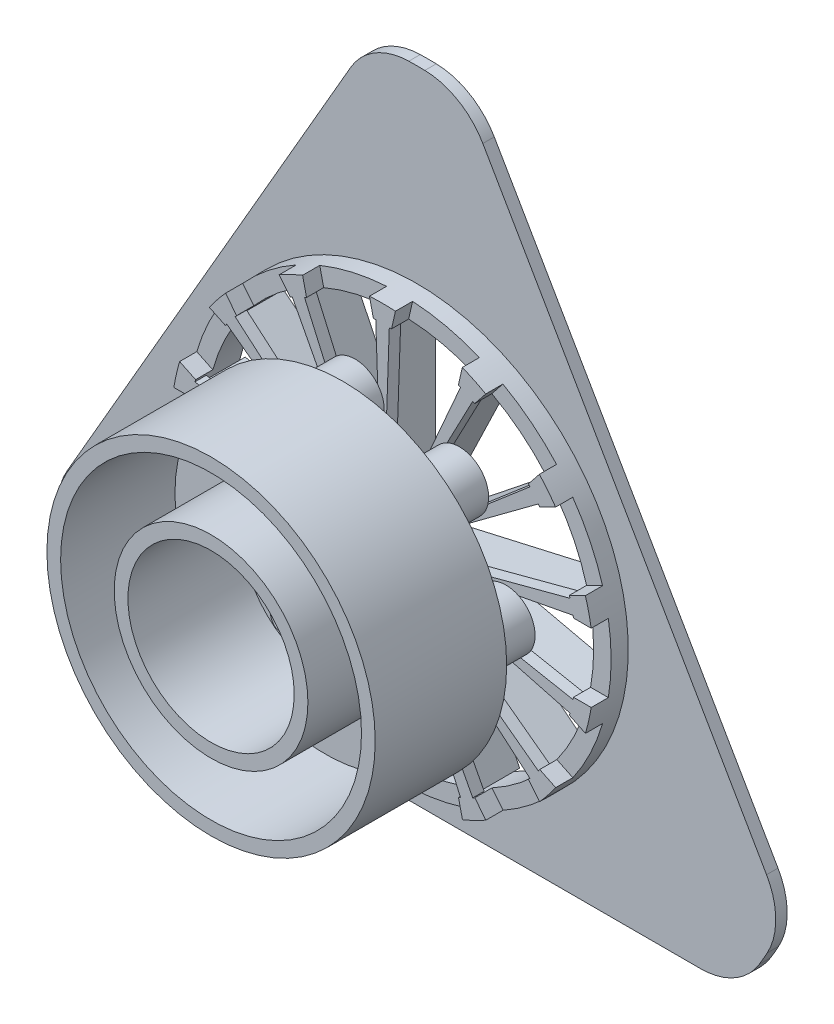
SolidWorks part; units mm, degrees
ref_plane "Спереди" through (0, 0, 0) normal (0, 0, 1) x (1, 0, 0)
ref_plane "Сверху" through (0, 0, 0) normal (0, 1, 0) x (1, 0, 0)
ref_plane "Справа" through (0, 0, 0) normal (1, 0, 0) x (0, 0, -1)
sketch "Sketch1" plane through (0, 0, 0) normal (0, 0, 1) x (1, 0, 0)
  line L0 (3.9, 6.755) -> (7.8, 0) construction
  line L2 (5.85, 10.1325) -> (11.7, 0) construction
  line L4 (7.8, 13.51) -> (15.6, 0) construction
  circle A61 centre (0, 0) radius 20
  circle A131 centre (0, 0) radius 1.25
  circle A484 centre (3.9, 0) radius 1.25
  circle A485 centre (7.8, 0) radius 1.25
  circle A486 centre (11.7, 0) radius 1.25
  circle A487 centre (15.6, 0) radius 1.25
  circle A488 centre (1.95, -3.3775) radius 1.25
  circle A489 centre (3.9, -6.755) radius 1.25
  circle A490 centre (5.85, -10.1325) radius 1.25
  circle A491 centre (7.8, -13.51) radius 1.25
  circle A492 centre (-1.95, -3.3775) radius 1.25
  circle A493 centre (-3.9, -6.755) radius 1.25
  circle A494 centre (-5.85, -10.1325) radius 1.25
  circle A495 centre (-7.8, -13.51) radius 1.25
  circle A496 centre (-3.9, 0) radius 1.25
  circle A497 centre (-7.8, 0) radius 1.25
  circle A498 centre (-11.7, 0) radius 1.25
  circle A499 centre (-15.6, 0) radius 1.25
  circle A500 centre (-1.95, 3.3775) radius 1.25
  circle A501 centre (-3.9, 6.755) radius 1.25
  circle A502 centre (-5.85, 10.1325) radius 1.25
  circle A503 centre (-7.8, 13.51) radius 1.25
  circle A504 centre (1.95, 3.3775) radius 1.25
  circle A505 centre (3.9, 6.755) radius 1.25
  circle A506 centre (5.85, 10.1325) radius 1.25
  circle A507 centre (7.8, 13.51) radius 1.25
  circle A508 centre (5.85, 3.3775) radius 1.25
  circle A509 centre (7.8, 6.755) radius 1.25
  circle A510 centre (9.75, 3.3775) radius 1.25
  circle A511 centre (11.7, 6.755) radius 1.25
  circle A512 centre (9.7491, 10.1341) radius 1.25
  circle A513 centre (13.6509, 3.3759) radius 1.25
  circle A514 centre (5.85, -3.3791) radius 1.25
  circle A515 centre (9.75, -3.3791) radius 1.25
  circle A516 centre (7.8, -6.7566) radius 1.25
  circle A517 centre (11.7, -6.7566) radius 1.25
  circle A518 centre (9.7491, -10.1356) radius 1.25
  circle A519 centre (13.6509, -3.3775) radius 1.25
  circle A520 centre (-0.0013, -6.7573) radius 1.25
  circle A521 centre (1.9487, -10.1348) radius 1.25
  circle A522 centre (-1.9513, -10.1348) radius 1.25
  circle A523 centre (-0.0013, -13.5123) radius 1.25
  circle A524 centre (-3.9032, -13.5123) radius 1.25
  circle A525 centre (3.9005, -13.5123) radius 1.25
  circle A526 centre (-5.8527, -3.3791) radius 1.25
  circle A527 centre (-7.8027, -6.7566) radius 1.25
  circle A528 centre (-9.7527, -3.3791) radius 1.25
  circle A529 centre (-11.7027, -6.7566) radius 1.25
  circle A530 centre (-13.6536, -3.3775) radius 1.25
  circle A531 centre (-9.7518, -10.1356) radius 1.25
  circle A532 centre (-5.8527, 3.3775) radius 1.25
  circle A533 centre (-9.7527, 3.3775) radius 1.25
  circle A534 centre (-7.8027, 6.755) radius 1.25
  circle A535 centre (-11.7027, 6.755) radius 1.25
  circle A536 centre (-9.7518, 10.1341) radius 1.25
  circle A537 centre (-13.6536, 3.3759) radius 1.25
  circle A538 centre (-0.0014, 6.7558) radius 1.25
  circle A539 centre (-1.9514, 10.1333) radius 1.25
  circle A540 centre (1.9486, 10.1333) radius 1.25
  circle A541 centre (-0.0014, 13.5108) radius 1.25
  circle A542 centre (3.9005, 13.5108) radius 1.25
  circle A543 centre (-3.9032, 13.5108) radius 1.25
  circle A544 centre (13.65, -1.1258) radius 2.2517 construction
  circle A545 centre (11.7009, -4.5044) radius 2.2522 construction
  circle A546 centre (9.75, -7.8834) radius 2.2522 construction
  circle A547 centre (7.7987, -11.2591) radius 2.2509 construction
  circle A548 centre (13.65, -1.1258) radius 0.65
  circle A549 centre (11.7009, -4.5044) radius 0.65
  circle A550 centre (9.75, -7.8834) radius 0.65
  circle A551 centre (7.7987, -11.2591) radius 0.65
  circle A552 centre (9.75, -1.1258) radius 0.65
  circle A553 centre (7.8009, -4.5044) radius 0.65
  circle A554 centre (5.85, -7.8834) radius 0.65
  circle A555 centre (3.8987, -11.2591) radius 0.65
  circle A556 centre (5.85, -1.1258) radius 0.65
  circle A557 centre (3.9009, -4.5044) radius 0.65
  circle A558 centre (1.95, -7.8834) radius 0.65
  circle A559 centre (-0.0013, -11.2591) radius 0.65
  circle A560 centre (1.95, -1.1258) radius 0.65
  circle A561 centre (0.0009, -4.5044) radius 0.65
  circle A562 centre (-1.95, -7.8834) radius 0.65
  circle A563 centre (-3.9013, -11.2591) radius 0.65
  circle A564 centre (-1.95, -1.1258) radius 0.65
  circle A565 centre (-3.8991, -4.5044) radius 0.65
  circle A566 centre (-5.85, -7.8834) radius 0.65
  circle A567 centre (-7.8013, -11.2591) radius 0.65
  circle A568 centre (-5.85, -1.1258) radius 0.65
  circle A569 centre (-7.7991, -4.5044) radius 0.65
  circle A570 centre (-9.75, -7.8834) radius 0.65
  circle A572 centre (-9.75, -1.1258) radius 0.65
  circle A573 centre (-11.6991, -4.5044) radius 0.65
  circle A576 centre (-13.65, -1.1258) radius 0.65
  circle A587 centre (0, 2.2517) radius 2.2517 construction
  circle A588 centre (0, 2.2517) radius 0.65
  circle A589 centre (3.9, 2.2517) radius 0.65
  circle A590 centre (7.8, 2.2517) radius 0.65
  circle A591 centre (11.7, 2.2517) radius 0.65
  circle A592 centre (15.6, 2.2517) radius 0.65
  circle A593 centre (1.9491, 5.6297) radius 2.2522 construction
  circle A594 centre (1.9491, 5.6297) radius 0.65
  circle A595 centre (5.8491, 5.6297) radius 0.65
  circle A596 centre (9.7491, 5.6297) radius 0.65
  circle A597 centre (13.6491, 5.6297) radius 0.65
  circle A598 centre (3.8991, 9.0072) radius 2.2522 construction
  circle A599 centre (3.8991, 9.0072) radius 0.65
  circle A600 centre (7.7991, 9.0072) radius 0.65
  circle A601 centre (11.6991, 9.0072) radius 0.65
  circle A602 centre (5.85, 12.3842) radius 2.2517 construction
  circle A603 centre (5.85, 12.3842) radius 0.65
  circle A604 centre (9.75, 12.3842) radius 0.65
  circle A605 centre (5.85, -14.6358) radius 0.65
  circle A606 centre (1.9509, -14.6353) radius 0.65
  circle A607 centre (-1.9491, -14.6353) radius 0.65
  circle A608 centre (-5.85, -14.6358) radius 0.65
  circle A609 centre (-15.6, 2.2517) radius 0.65
  circle A610 centre (-13.65, 5.6281) radius 0.65
  circle A611 centre (-11.7, 9.0056) radius 0.65
  circle A612 centre (-9.75, 12.3842) radius 0.65
  circle A613 centre (-5.85, 12.3842) radius 0.65
  circle A614 centre (-1.95, 12.3842) radius 0.65
  circle A615 centre (1.95, 12.3842) radius 0.65
  circle A616 centre (-7.8, 9.0056) radius 0.65
  circle A617 centre (-9.75, 5.6281) radius 0.65
  circle A618 centre (-11.7, 2.2517) radius 0.65
  circle A619 centre (-3.9, 9.0056) radius 0.65
  circle A620 centre (-5.85, 5.6281) radius 0.65
  circle A621 centre (-7.8, 2.2517) radius 0.65
  circle A622 centre (0, 9.0056) radius 0.65
  circle A623 centre (-1.95, 5.6281) radius 0.65
  circle A624 centre (-3.9, 2.2517) radius 0.65
  circle A625 centre (-15.5991, -4.5044) radius 0.65
  circle A626 centre (-13.65, -7.8834) radius 0.65
  circle A627 centre (-17.55, -7.8834) radius 0.65
  circle A628 centre (-19.5013, -11.2591) radius 0.65
  circle A629 centre (-15.6013, -11.2591) radius 0.65
  circle A630 centre (-11.7013, -11.2591) radius 0.65
  point P51 (0, 0)
  point P125 (-0.0013, -0.0008)
  point P231 (0, 0)
  dimension "D1" = 5
  dimension "D3" = 6
  dimension "D5" = 8
  dimension "D7" = 4
  dimension "D11" = 4
  dimension "D2" = 6
  dimension "D6" = 5
  dimension "D8" = 3
  dimension "D9" = 2
  dimension "D4" = 1.3
  dimension "D10" = 3
ref_plane "Plane1" through (0, 0, 10) normal (0, 0, 1) x (1, 0, 0)
sketch "Sketch2" plane through (0, 0, 10) normal (0, 0, 1) x (1, 0, 0)
  line L0 (0, 15.7191) -> (0, 7.2245) construction
  line L62 (-0.15, 16.9697) -> (-0.15, 0.6837)
  line L71 (0.15, 16.9697) -> (0.15, 0.6837)
  line L92 (7.498, 15.2241) -> (0.4318, 0.5509)
  line L101 (7.2278, 15.3543) -> (0.1615, 0.6811)
  line L110 (13.361, 10.4632) -> (0.6281, 0.309)
  line L119 (13.174, 10.6977) -> (0.441, 0.5436)
  line L124 (16.5777, 3.6299) -> (0.7, 0.0059)
  line L133 (16.5109, 3.9224) -> (0.6332, 0.2984)
  line L142 (16.5109, -3.9224) -> (0.6332, -0.2984)
  line L151 (16.5777, -3.6299) -> (0.7, -0.0059)
  line L160 (13.174, -10.6977) -> (0.441, -0.5436)
  line L165 (13.361, -10.4632) -> (0.6281, -0.309)
  line L168 (7.2278, -15.3543) -> (0.1615, -0.6811)
  line L171 (7.498, -15.2241) -> (0.4318, -0.5509)
  line L174 (-0.15, -16.9697) -> (-0.15, -0.6837)
  line L177 (0.15, -16.9697) -> (0.15, -0.6837)
  line L180 (-7.498, -15.2241) -> (-0.4318, -0.5509)
  line L183 (-7.2278, -15.3543) -> (-0.1615, -0.6811)
  line L186 (-13.361, -10.4632) -> (-0.6281, -0.309)
  line L189 (-13.174, -10.6977) -> (-0.441, -0.5436)
  line L192 (-16.5777, -3.6299) -> (-0.7, -0.0059)
  line L193 (-16.5109, -3.9224) -> (-0.6332, -0.2984)
  line L194 (-16.5109, 3.9224) -> (-0.6332, 0.2984)
  line L195 (-16.5777, 3.6299) -> (-0.7, 0.0059)
  line L196 (-13.174, 10.6977) -> (-0.441, 0.5436)
  line L197 (-13.361, 10.4632) -> (-0.6281, 0.309)
  line L198 (-7.2278, 15.3543) -> (-0.1615, 0.6811)
  line L199 (-7.498, 15.2241) -> (-0.4318, 0.5509)
  circle A52 centre (0, 0) radius 16.9704
  circle A53 centre (0, 0) radius 18.5
  circle A199 centre (0, 0) radius 0.7
  point P62 (0, 0)
  dimension "D1" = 0.3
extrude "Boss-Extrude10" add sketch "Sketch2" along normal blind 4 contours A53 A52 | A199 L71 A52 L62 | A199 L92 A52 L101 | A199 L110 A52 L119 | A199 L124 A52 L133 | A199 L142 A52 L151 | A199 L160 A52 L165 | A199 L168 A52 L171 | A199 L174 A52 L177 | A199 L180 A52 L183 | A199 L186 A52 L189 | A199 L192 A52 L193 | A199 L196 A52 L197 | A199 L198 A52 L199 | A199 L194 A52 L195 | A199 region at (0, 8.8324, 10) region at (0, 0, 10) region at (-3.8322, 7.9577, 10) region at (3.8322, 7.9577, 10) region at (-6.9054, 5.5069, 10) region at (6.9054, 5.5069, 10) region at (-8.6109, 1.9654, 10) region at (8.6109, 1.9654, 10) region at (-8.6109, -1.9654, 10) region at (8.6109, -1.9654, 10) region at (-6.9054, -5.5069, 10) region at (6.9054, -5.5069, 10) region at (-3.8322, -7.9577, 10) region at (3.8322, -7.9577, 10) region at (0, -8.8324, 10) region at (-17.9767, 0, 10)
sketch "Sketch8" plane through (0, 0, 14) normal (0, 0, 1) x (1, 0, 0)
  circle A0 centre (0, 0) radius 21.2494
  circle A1 centre (0, 0) radius 22.6785
extrude "Boss-Extrude11" add sketch "Sketch8" against normal blind 4 separate body
sketch "Sketch9" plane through (0, 0, 14) normal (0, 0, 1) x (1, 0, 0)
  line L0 (-7.2278, 15.3543) -> (-0.1615, 0.6811) construction
  line L2 (13.361, 10.4632) -> (0.6281, 0.309) construction
  line L3 (7.2278, 15.3543) -> (0.1615, 0.6811) construction
  line L7 (-13.361, 10.4632) -> (-0.6281, 0.309) construction
  circle A0 centre (1.4743, 6.4592) radius 1.6243
  circle A1 centre (1.4743, 6.4592) radius 1.1243
  circle A2 centre (5.9692, 2.8746) radius 1.6243
  circle A3 centre (5.9692, 2.8746) radius 1.1243
  circle A4 centre (5.9692, -2.8746) radius 1.6243
  circle A5 centre (5.9692, -2.8746) radius 1.1243
  circle A6 centre (1.4743, -6.4592) radius 1.6243
  circle A7 centre (1.4743, -6.4592) radius 1.1243
  circle A8 centre (-4.1308, -5.1798) radius 1.6243
  circle A9 centre (-4.1308, -5.1798) radius 1.1243
  circle A10 centre (-6.6253, 0) radius 1.6243
  circle A11 centre (-6.6253, 0) radius 1.1243
  circle A12 centre (-4.1308, 5.1798) radius 1.6243
  circle A13 centre (-4.1308, 5.1798) radius 1.1243
  circle A14 centre (6.731, 8.4404) radius 2.5523
  circle A15 centre (6.731, 8.4404) radius 2.5523
  circle A16 centre (6.731, 8.4404) radius 2.0523
  circle A17 centre (10.7957, 0) radius 2.0523
  circle A18 centre (10.7957, 0) radius 2.5523
  circle A19 centre (6.731, -8.4404) radius 2.0523
  circle A20 centre (6.731, -8.4404) radius 2.5523
  circle A21 centre (-2.4023, -10.5251) radius 2.0523
  circle A22 centre (-2.4023, -10.5251) radius 2.5523
  circle A23 centre (-9.7266, -4.6841) radius 2.0523
  circle A24 centre (-9.7266, -4.6841) radius 2.5523
  circle A25 centre (-9.7266, 4.6841) radius 2.0523
  circle A26 centre (-9.7266, 4.6841) radius 2.5523
  circle A27 centre (-2.4023, 10.5251) radius 2.0523
  circle A28 centre (-2.4023, 10.5251) radius 2.5523
  point P24 (0, 0)
  point P30 (0, 0)
  point P31 (6.4938, 8.1493)
  point P51 (0, 0)
  point P57 (6.8199, 8.5519)
  point P58 (0, -0.3643)
  point P59 (0, 0)
  point P60 (0, 0)
  point P62 (1.4361, 6.3255)
  point P63 (1.629, 6.6904)
  point P64 (1.5046, 6.5918)
  point P65 (1.4701, 5.9808)
  dimension "D3" = 0.5
  dimension "D4" = 0.5
  dimension "D1" = 7
  dimension "D2" = 7
extrude "Boss-Extrude12" add sketch "Sketch9" along normal blind 5 contours A0 A1 | A14 A16 | A28 A27 | A12 A13 | A26 A25 | A10 A11 | A24 A23 | A8 A9 | A22 A21 | A20 A19 | A4 A5 | A6 A7 | A2 A3 | A18 A17 region at (-0.1041, 6.4592, 14) region at (4.3908, 2.8746, 14) region at (4.3908, -2.8746, 14) region at (-0.1041, -6.4592, 14) region at (-5.7091, -5.1798, 14) region at (-8.2036, 0, 14) region at (-5.7091, 5.1798, 14) region at (4.2509, 8.4404, 14) region at (8.3156, 0, 14) region at (4.2509, -8.4404, 14) region at (-4.8824, -10.5251, 14) region at (-12.2067, -4.6841, 14) region at (-12.2067, 4.6841, 14) region at (-4.8824, 10.5251, 14)
sketch "Sketch11" plane through (0, 0, 19) normal (0, 0, 1) x (1, 0, 0)
  circle A0 centre (0, 0) radius 8.1149
  circle A2 centre (0, 0) radius 4.8946
  circle A3 centre (0, 0) radius 14.3613
  circle M6 centre (10.7957, 0) radius 2.0523
  circle M7 centre (10.7957, 0) radius 2.5523
extrude "Boss-Extrude16" add sketch "Sketch11" against normal blind 1.5 contours A2 | A0 A2 | A3 A0 M7 | M6 region at (-7.8854, 0, 19) region at (0, 0, 19) region at (-13.9551, 0, 19) region at (10.7957, 0, 19)
sketch "Sketch12" plane through (0, 0, 19) normal (0, 0, 1) x (1, 0, 0)
  circle A0 centre (0, 0) radius 7.2737
  circle A1 centre (0, 0) radius 8.4737
  circle A2 centre (0, 0) radius 14.3613
  circle A3 centre (0, 0) radius 13.1613
  circle A6 centre (0, 0) radius 14.3613 construction
  dimension "D1" = 1.2
  dimension "D2" = 1.2
extrude "Boss-Extrude14" add sketch "Sketch12" along normal blind 10 contours A1 A0 | A2 A3 region at (-8.234, 0, 19) region at (-13.9551, 0, 19)
sketch "Sketch13" plane through (0, 0, 19) normal (0, 0, 1) x (1, 0, 0)
  circle A0 centre (1.355, 6.1475) radius 0.9
  circle A1 centre (5.6511, 2.7735) radius 0.9
  circle A2 centre (5.6919, -2.689) radius 0.9
  circle A3 centre (1.4465, -6.1266) radius 0.9
  circle A4 centre (-3.8881, -4.9508) radius 0.9
  circle A5 centre (-6.2949, -0.0469) radius 0.9
  circle A6 centre (-3.9615, 4.8923) radius 0.9
  circle A7 centre (-2.4023, 10.5251) radius 0.9
  circle A8 centre (6.8199, 8.5519) radius 0.9
  circle A9 centre (11.0272, 0.1115) radius 0.9
  circle A10 centre (7.0513, -8.4404) radius 0.9
  circle A11 centre (-2.1137, -10.664) radius 0.9
  circle A12 centre (-9.5664, -4.8849) radius 0.9
  circle A13 centre (-9.6949, 4.5451) radius 0.9
  point P4 (1.355, 6.1475)
  point P17 (0, 0)
  point P32 (0.1602, -0.0366)
extrude "Cut-Extrude2" cut sketch "Sketch13" against normal blind 1.5
sketch "Sketch16" plane through (0, 0, 10) normal (0, 0, -1) x (-1, 0, 0)
  line L0 (0, 0) -> (-0.5923, 16.9601)
  line L1 (0, 0) -> (0.5923, 16.9601)
  line L2 (0, 0) -> (7.8923, 15.0235)
  line L3 (0, 0) -> (6.8251, 15.5375)
  line L4 (0, 0) -> (13.6292, 10.1114)
  line L5 (0, 0) -> (12.8907, 11.0375)
  line L6 (0, 0) -> (16.6666, 3.1966)
  line L7 (0, 0) -> (16.4031, 4.3514)
  line L8 (0, 0) -> (16.4031, -4.3514)
  line L9 (0, 0) -> (16.6666, -3.1966)
  line L10 (0, 0) -> (12.8907, -11.0375)
  line L11 (0, 0) -> (13.6292, -10.1114)
  line L12 (0, 0) -> (6.8251, -15.5375)
  line L13 (0, 0) -> (7.8923, -15.0235)
  line L14 (0, 0) -> (-0.5923, -16.9601)
  line L15 (0, 0) -> (0.5923, -16.9601)
  line L16 (0, 0) -> (-7.8923, -15.0235)
  line L17 (0, 0) -> (-6.8251, -15.5375)
  line L18 (0, 0) -> (-13.6292, -10.1114)
  line L19 (0, 0) -> (-12.8907, -11.0375)
  line L20 (0, 0) -> (-16.6666, -3.1966)
  line L21 (0, 0) -> (-16.4031, -4.3514)
  line L22 (0, 0) -> (-16.4031, 4.3514)
  line L23 (0, 0) -> (-16.6666, 3.1966)
  line L24 (0, 0) -> (-12.8907, 11.0375)
  line L25 (0, 0) -> (-13.6292, 10.1114)
  line L26 (0, 0) -> (-6.8251, 15.5375)
  line L27 (0, 0) -> (-7.8923, 15.0235)
  arc A0 (-0.15, 16.9697) -> (-7.2278, 15.3543) centre (0, 0) ccw construction
  arc A1 (7.2278, 15.3543) -> (0.15, 16.9697) centre (0, 0) ccw construction
  arc A2 (-0.5923, 16.9601) -> (0.5923, 16.9601) centre (0, 0) cw
  arc A3 (6.8251, 15.5375) -> (7.8923, 15.0235) centre (0, 0) cw
  arc A4 (12.8907, 11.0375) -> (13.6292, 10.1114) centre (0, 0) cw
  arc A5 (16.4031, 4.3514) -> (16.6666, 3.1966) centre (0, 0) cw
  arc A6 (16.6666, -3.1966) -> (16.4031, -4.3514) centre (0, 0) cw
  arc A7 (13.6292, -10.1114) -> (12.8907, -11.0375) centre (0, 0) cw
  arc A8 (7.8923, -15.0235) -> (6.8251, -15.5375) centre (0, 0) cw
  arc A9 (0.5923, -16.9601) -> (-0.5923, -16.9601) centre (0, 0) cw
  arc A10 (-6.8251, -15.5375) -> (-7.8923, -15.0235) centre (0, 0) cw
  arc A11 (-12.8907, -11.0375) -> (-13.6292, -10.1114) centre (0, 0) cw
  arc A12 (-16.4031, -4.3514) -> (-16.6666, -3.1966) centre (0, 0) cw
  arc A13 (-16.6666, 3.1966) -> (-16.4031, 4.3514) centre (0, 0) cw
  arc A14 (-13.6292, 10.1114) -> (-12.8907, 11.0375) centre (0, 0) cw
  arc A15 (-7.8923, 15.0235) -> (-6.8251, 15.5375) centre (0, 0) cw
  point P52 (0, 0)
  dimension "D1" = 14
extrude "Boss-Extrude17" add sketch "Sketch16" along normal blind 1 from surface contours A15 L27 L26 | A2 L0 L1 | A3 L3 L2 | A4 L5 L4 | A5 L7 L6 | A6 L9 L8 | A7 L11 L10 | A8 L13 L12 | A9 L15 L14 | A10 L17 L16 | A12 L21 L20 | A11 L19 L18 | A13 L23 L22 | A14 L25 L24 region at (0, 11.3113, 10) region at (-4.9078, 10.1911, 10) region at (-8.8435, 7.0525, 10) region at (-11.0277, 2.517, 10) region at (-11.0277, -2.517, 10) region at (-8.8435, -7.0525, 10) region at (-4.9078, -10.1911, 10) region at (0, -11.3113, 10) region at (4.9078, -10.1911, 10) region at (8.8435, -7.0525, 10) region at (11.0277, -2.517, 10) region at (11.0277, 2.517, 10) region at (8.8435, 7.0525, 10) region at (4.9078, 10.1911, 10) starting at face at (-6.5894, 5.2551, 14)
ref_plane "Plane2" through (22.6785, 0, 0) normal (1, 0, 0) x (0, 0, -1)
sketch "Sketch17" plane through (22.6785, 0, 0) normal (1, 0, 0) x (0, 0, -1)
  line L0 (-14, 0.0059) -> (-10, 0.0059) construction
  line L1 (-14.4721, 3.0059) -> (-12.5, 3.0059)
  line L2 (-14.4721, 3.0059) -> (-14.4721, -2.9941)
  line L3 (-14.4721, -2.9941) -> (-12.5, -2.9941)
  line L4 (-12.5, 3.0059) -> (-12.5, -2.9941)
  line L5 (-14.4721, 3.0059) -> (-12.5, -2.9941) construction
  line L6 (-14.4721, -2.9941) -> (-12.5, 3.0059) construction
  line L7 (-10, -22.6785) -> (-10, 22.6785) construction
  point P0 (-13.4861, 0.0059)
  dimension "D1" = 2.5
extrude "Cut-Extrude4" cut sketch "Sketch17" against normal blind 5 from offset 2 offset against normal yes
pattern_circular "CirPattern1" count 14 over 360 of "Cut-Extrude4"
sketch "Sketch18" plane through (0, 0, 19) normal (0, 0, 1) x (1, 0, 0)
  circle A0 centre (0, 0) radius 21.2494
  circle A1 centre (0, 0) radius 22.6785
extrude "Cut-Extrude5" cut sketch "Sketch18" against normal through all both and the other way through all
sketch "Sketch19" plane through (0, 0, 10) normal (0, 0, -1) x (-1, 0, 0)
  circle A0 centre (0, 0) radius 18.5
  circle A1 centre (0, 0) radius 22.1002
extrude "Boss-Extrude18" add sketch "Sketch19" against normal blind 1
sketch "Sketch3" plane through (0, 0, 11) normal (0, 0, 1) x (1, 0, 0)
  circle A0 centre (0, 0) radius 21.3923
  circle A1 centre (0, 0) radius 35
extrude "Boss-Extrude2" add sketch "Sketch3" against normal blind 1 contours A1 region at (-34.0101, 0, 11)
sketch "Sketch4" plane through (0, 0, 10) normal (0, 0, -1) x (-1, 0, 0)
  circle A0 centre (0, 0) radius 29 construction
  circle A1 centre (0, 29) radius 2.9
  circle A2 centre (25.1147, -14.5) radius 2.9
  circle A3 centre (-25.1147, -14.5) radius 2.9
  point P11 (0, 0)
  dimension "D1" = 3
extrude "Boss-Extrude3" add sketch "Sketch4" along normal blind 2
sketch "Sketch6" plane through (0, 0, 10) normal (0, 0, 1) x (1, 0, 0)
  circle A0 centre (0, 30) radius 5
  circle A2 centre (25.9808, -15) radius 5
  circle A3 centre (-25.9808, -15) radius 5
  point P10 (0, 0)
  dimension "D1" = 3
extrude "Boss-Extrude4" add sketch "Sketch6" along normal blind 1
sketch "Sketch7" plane through (0, 0, 8) normal (0, 0, -1) x (-1, 0, 0)
  line L1 (0, 42) -> (-36.3731, -21)
  line L2 (-36.3731, -21) -> (36.3731, -21)
  line L3 (36.3731, -21) -> (0, 42)
  circle A2 centre (0, 0) radius 21 construction
  circle A3 centre (0, 0) radius 59.1314
extrude "Cut-Extrude1" cut sketch "Sketch7" against normal blind 10
fillet "Fillet1" radius 6 6 edges at (-4.1865, 34.7487, 10.5) (28, -21, 10.5) (-28, -21, 10.5) (4.1865, 34.7487, 10.5) (-32.1865, -13.7487, 10.5) (32.1865, -13.7487, 10.5)
sketch "Sketch20" plane through (0, 0, 10) normal (0, 0, 1) x (1, 0, 0)
  line L0 (0, 15.7191) -> (0, 7.2245) construction
  line L62 (-0.15, 16.9697) -> (-0.15, 0.6837)
  line L71 (0.15, 16.9697) -> (0.15, 0.6837)
  line L92 (7.498, 15.2241) -> (0.4318, 0.5509)
  line L101 (7.2278, 15.3543) -> (0.1615, 0.6811)
  line L110 (13.361, 10.4632) -> (0.6281, 0.309)
  line L119 (13.174, 10.6977) -> (0.441, 0.5436)
  line L124 (16.5777, 3.6299) -> (0.7, 0.0059)
  line L133 (16.5109, 3.9224) -> (0.6332, 0.2984)
  line L142 (16.5109, -3.9224) -> (0.6332, -0.2984)
  line L151 (16.5777, -3.6299) -> (0.7, -0.0059)
  line L160 (13.174, -10.6977) -> (0.441, -0.5436)
  line L165 (13.361, -10.4632) -> (0.6281, -0.309)
  line L168 (7.2278, -15.3543) -> (0.1615, -0.6811)
  line L171 (7.498, -15.2241) -> (0.4318, -0.5509)
  line L174 (-0.15, -16.9697) -> (-0.15, -0.6837)
  line L177 (0.15, -16.9697) -> (0.15, -0.6837)
  line L180 (-7.498, -15.2241) -> (-0.4318, -0.5509)
  line L183 (-7.2278, -15.3543) -> (-0.1615, -0.6811)
  line L186 (-13.361, -10.4632) -> (-0.6281, -0.309)
  line L189 (-13.174, -10.6977) -> (-0.441, -0.5436)
  line L192 (-16.5777, -3.6299) -> (-0.7, -0.0059)
  line L193 (-16.5109, -3.9224) -> (-0.6332, -0.2984)
  line L194 (-16.5109, 3.9224) -> (-0.6332, 0.2984)
  line L195 (-16.5777, 3.6299) -> (-0.7, 0.0059)
  line L196 (-13.174, 10.6977) -> (-0.441, 0.5436)
  line L197 (-13.361, 10.4632) -> (-0.6281, 0.309)
  line L198 (-7.2278, 15.3543) -> (-0.1615, 0.6811)
  line L199 (-7.498, 15.2241) -> (-0.4318, 0.5509)
  circle A52 centre (0, 0) radius 16.9704
  circle A53 centre (0, 0) radius 18.5
  circle A199 centre (0, 0) radius 0.7
  point P62 (0, 0)
  dimension "D1" = 0.3
extrude "Boss-Extrude19" add sketch "Sketch20" against normal blind 0.5 contours L71 A199 L62 A52 | L198 A199 L199 A52 | L196 A199 L197 A52 | L194 A199 L195 A52 | L192 A199 L193 A52 | L186 A199 L189 A52 | L180 A199 L183 A52 | L174 A199 L177 A52 | L168 A199 L171 A52 | L160 A199 L165 A52 | L142 A199 L151 A52 | L124 A199 L133 A52 | L92 A199 L101 A52 | L110 A199 L119 A52 region at (0, 8.8324, 10) region at (-3.8322, 7.9577, 10) region at (3.8322, 7.9577, 10) region at (-6.9054, 5.5069, 10) region at (6.9054, 5.5069, 10) region at (-8.6109, 1.9654, 10) region at (8.6109, 1.9654, 10) region at (-8.6109, -1.9654, 10) region at (8.6109, -1.9654, 10) region at (-6.9054, -5.5069, 10) region at (6.9054, -5.5069, 10) region at (-3.8322, -7.9577, 10) region at (3.8322, -7.9577, 10) region at (0, -8.8324, 10)
